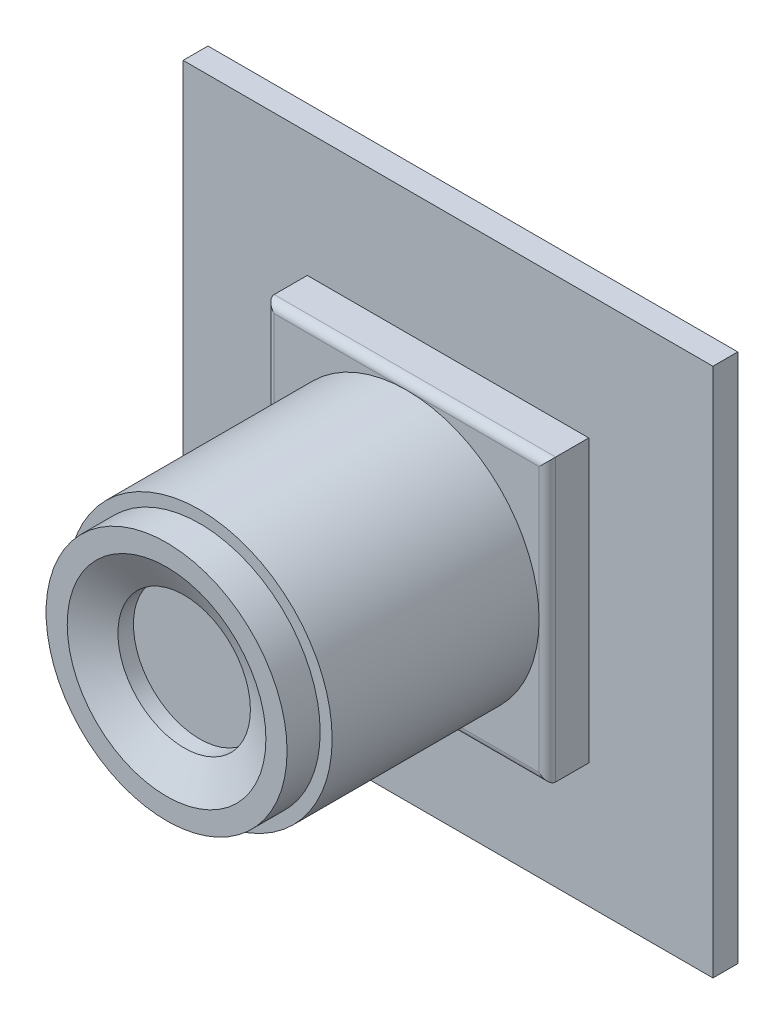
SolidWorks part; units mm, degrees
material "ABS"
ref_plane "Front Plane" through (0, 0, 0) normal (0, 0, 1) x (1, 0, 0)
ref_plane "Top Plane" through (0, 0, 0) normal (0, 1, 0) x (1, 0, 0)
ref_plane "Right Plane" through (0, 0, 0) normal (1, 0, 0) x (0, 0, -1)
sketch "Sketch1" plane through (0, 0, 0) normal (0, 0, 1) x (1, 0, 0)
  line L1 (-16, -16) -> (16, -16)
  line L2 (-16, -16) -> (-16, 16)
  line L3 (-16, 16) -> (16, 16)
  line L4 (16, -16) -> (16, 16)
  line L5 (-16, -16) -> (16, 16) construction
  line L6 (-16, 16) -> (16, -16) construction
  point P0 (0, 0)
  dimension "D1" = 32
  dimension "D2" = 32
extrude "Boss-Extrude1" add sketch "Sketch1" along normal blind 1.5
sketch "Sketch3" plane through (0, 0, 1.5) normal (0, 0, 1) x (1, 0, 0)
  line L1 (-8.5, -8.5) -> (8.5, -8.5)
  line L2 (-8.5, -8.5) -> (-8.5, 8.5)
  line L3 (-8.5, 8.5) -> (8.5, 8.5)
  line L4 (8.5, -8.5) -> (8.5, 8.5)
  line L5 (-8.5, -8.5) -> (8.5, 8.5) construction
  line L6 (-8.5, 8.5) -> (8.5, -8.5) construction
  point P0 (0, 0)
  dimension "D1" = 17
extrude "Boss-Extrude2" add sketch "Sketch3" along normal blind 2.5
sketch "Sketch4" plane through (0, 0, 4) normal (0, 0, 1) x (1, 0, 0)
  circle A0 centre (0, 0) radius 8
  dimension "D1" = 16
extrude "Boss-Extrude3" add sketch "Sketch4" along normal blind 12.5
sketch "Sketch5" plane through (0, 0, 16.5) normal (0, 0, 1) x (1, 0, 0)
  circle A0 centre (0, 0) radius 7.2778
extrude "Boss-Extrude4" add sketch "Sketch5" along normal blind 2
sketch "Sketch6" plane through (0, 0, 18.5) normal (0, 0, 1) x (1, 0, 0)
  circle A0 centre (0, 0) radius 4
  dimension "D1" = 8
extrude "Cut-Extrude1" cut sketch "Sketch6" against normal blind 2
chamfer "Chamfer1" distance 2 angle 28 1 edges at (4, 0, 18.5) first distance on face at (4, 0, 18.5)
fillet "Fillet2" radius 0.5 4 edges at (8.5, 0, 4) (0, -8.5, 4) (-8.5, 0, 4) (0, 8.5, 4)
